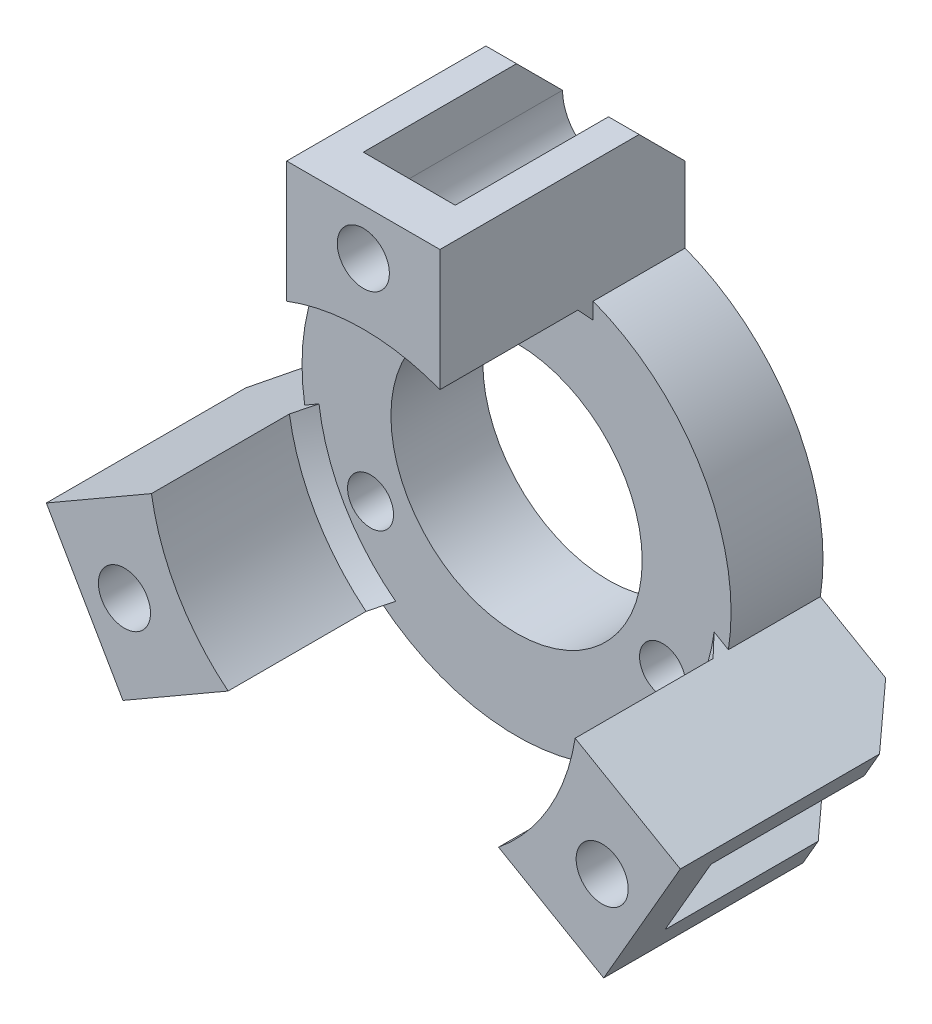
SolidWorks part; units mm, degrees
ref_plane "前基準面" through (0, 0, 0) normal (0, 0, 1) x (1, 0, 0)
ref_plane "上基準面" through (0, 0, 0) normal (0, 1, 0) x (1, 0, 0)
ref_plane "右基準面" through (0, 0, 0) normal (1, 0, 0) x (0, 0, -1)
sketch "草圖1" plane through (0, 0, 0) normal (0, 0, 1) x (1, 0, 0)
  circle A0 centre (0, 0) radius 8.2
  circle A1 centre (0, 0) radius 14
  dimension "D1" = 16.4
  dimension "D2" = 28
extrude "填料-伸長1" add sketch "草圖1" along normal blind 6
sketch "草圖2" plane through (0, 0, 0) normal (0, 0, 1) x (1, 0, 0)
  line L0 (0, 0) -> (0, 21) construction
  line L1 (20.6865, -6.1699) -> (13.8248, -2.2082)
  line L2 (-5, 21) -> (5, 21)
  line L3 (-5, 21) -> (-5, 13.0767)
  line L4 (20.6865, -6.1699) -> (15.6865, -14.8301)
  line L5 (5, 21) -> (5, 13.0767)
  line L6 (15.6865, -14.8301) -> (8.8248, -10.8685)
  line L7 (-15.6865, -14.8301) -> (-8.8248, -10.8685)
  line L8 (-15.6865, -14.8301) -> (-20.6865, -6.1699)
  line L9 (-20.6865, -6.1699) -> (-13.8248, -2.2082)
  arc A1 (-13.8248, -2.2082) -> (-8.8248, -10.8685) centre (0, 0) ccw
  arc A2 (8.8248, -10.8685) -> (13.8248, -2.2082) centre (0, 0) ccw
  arc A3 (5, 13.0767) -> (-5, 13.0767) centre (0, 0) ccw
  point P8 (0, 21)
  point P21 (0, 0)
  dimension "D1" = 21
  dimension "D2" = 10
  dimension "D3" = 3
extrude "填料-伸長2" add sketch "草圖2" along normal blind 16
sketch "草圖3" plane through (0, 0, 16) normal (0, 0, 1) x (1, 0, 0)
  line L0 (5, 21) -> (-5, 21) construction
  circle A0 centre (0, 18) radius 1.7
  circle A1 centre (15.5885, -9) radius 1.7
  circle A2 centre (-15.5885, -9) radius 1.7
  point P11 (0, 0)
  point P12 (0, 0)
  dimension "D1" = 3.4
  dimension "D2" = 3
  dimension "D3" = 18
  dimension "D4" = 3
extrude "除料-伸長1" cut sketch "草圖3" against normal through all
sketch "草圖4" plane through (0, 0, 0) normal (0, 0, -1) x (-1, 0, 0)
  circle A1 centre (0, 11) radius 1.5
  circle A2 centre (9.5263, -5.5) radius 1.5
  circle A3 centre (-9.5263, -5.5) radius 1.5
  point P11 (0, 0)
  dimension "D2" = 3
  dimension "D3" = 3
extrude "除料-伸長2" cut sketch "草圖4" against normal through all
sketch "草圖5" plane through (0, 0, 0) normal (0, 0, -1) x (-1, 0, 0)
  line L0 (-5, 21) -> (5, 21) construction
  line L1 (17.0885, -6.4019) -> (19.6865, -7.9019)
  line L2 (-3, 18) -> (-3, 21)
  line L3 (-3, 21) -> (3, 21)
  line L4 (3, 18) -> (3, 21)
  line L5 (19.6865, -7.9019) -> (16.6865, -13.0981)
  line L6 (14.0885, -11.5981) -> (16.6865, -13.0981)
  line L7 (-14.0885, -11.5981) -> (-16.6865, -13.0981)
  line L8 (-16.6865, -13.0981) -> (-19.6865, -7.9019)
  line L9 (-17.0885, -6.4019) -> (-19.6865, -7.9019)
  arc A0 (-3, 18) -> (3, 18) centre (0, 18) ccw
  arc A1 (17.0885, -6.4019) -> (14.0885, -11.5981) centre (15.5885, -9) ccw
  arc A2 (-14.0885, -11.5981) -> (-17.0885, -6.4019) centre (-15.5885, -9) ccw
  point P21 (0, 0)
  dimension "D1" = 6
  dimension "D2" = 3
extrude "除料-伸長3" cut sketch "草圖5" against normal blind 13
chamfer "導角1" distance 3 angle 45 6 edges at (4, 21, 0) (-4, 21, 0) (-20.1865, -7.0359, 0) (-16.1865, -13.9641, 0) (20.1865, -7.0359, 0) (16.1865, -13.9641, 0)
chamfer "導角2" distance 1 angle 45 3 edges at (0, 14, 6) (-12.1244, -7, 6) (12.1244, -7, 6)
